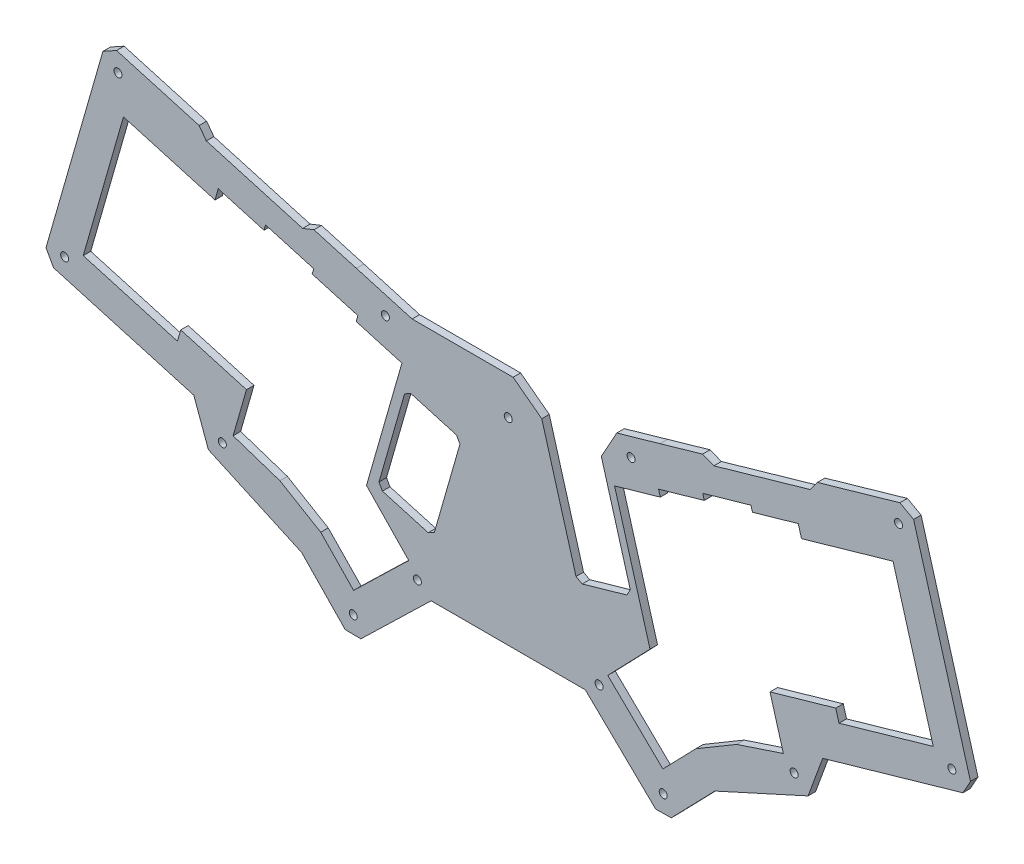
SolidWorks part; units mm, degrees
ref_plane "Plan de face" through (0, 0, 0) normal (0, 0, 1) x (1, 0, 0)
ref_plane "Plan de dessus" through (0, 0, 0) normal (0, 1, 0) x (1, 0, 0)
ref_plane "Plan de droite" through (0, 0, 0) normal (1, 0, 0) x (0, 0, -1)
sketch "Esquisse1" plane through (0, 0, 0) normal (0, 0, 1) x (1, 0, 0)
  line L0 (-121.6461, -32.0475) -> (-108.1875, -28.1884) construction
  line L1 (-108.1875, -28.1884) -> (-104.3283, -41.647) construction
  line L2 (-104.3283, -41.647) -> (-117.7869, -45.5062) construction
  line L3 (-117.7869, -45.5062) -> (-121.6461, -32.0475) construction
  line L4 (-100.1763, -37.9855) -> (-104.0355, -24.5269) construction
  line L5 (-104.0355, -24.5269) -> (-90.5769, -20.6677) construction
  line L6 (-90.5769, -20.6677) -> (-86.7177, -34.1263) construction
  line L7 (-86.7177, -34.1263) -> (-100.1763, -37.9855) construction
  line L8 (-82.5657, -30.4649) -> (-86.4249, -17.0063) construction
  line L9 (-86.4249, -17.0063) -> (-72.9663, -13.1471) construction
  line L10 (-72.9663, -13.1471) -> (-69.1071, -26.6057) construction
  line L11 (-69.1071, -26.6057) -> (-82.5657, -30.4649) construction
  line L12 (-63.6458, -27.5106) -> (-67.505, -14.0519) construction
  line L13 (-67.505, -14.0519) -> (-54.0463, -10.1927) construction
  line L14 (-54.0463, -10.1927) -> (-50.1872, -23.6514) construction
  line L15 (-50.1872, -23.6514) -> (-63.6458, -27.5106) construction
  line L16 (-44.0711, -26.8394) -> (-47.9303, -13.3808) construction
  line L17 (-47.9303, -13.3808) -> (-34.4717, -9.5216) construction
  line L18 (-34.4717, -9.5216) -> (-30.6125, -22.9802) construction
  line L19 (-30.6125, -22.9802) -> (-44.0711, -26.8394) construction
  line L20 (-25.8054, -21.6018) -> (-29.6646, -8.1432) construction
  line L21 (-29.6646, -8.1432) -> (-16.206, -4.284) construction
  line L22 (-16.206, -4.284) -> (-12.3468, -17.7426) construction
  line L23 (-12.3468, -17.7426) -> (-25.8054, -21.6018) construction
  line L24 (-116.4086, -50.3128) -> (-102.95, -46.4536) construction
  line L25 (-102.95, -46.4536) -> (-99.0908, -59.9122) construction
  line L26 (-99.0908, -59.9122) -> (-112.5494, -63.7714) construction
  line L27 (-112.5494, -63.7714) -> (-116.4086, -50.3128) construction
  line L28 (-98.798, -42.7922) -> (-85.3394, -38.933) construction
  line L29 (-85.3394, -38.933) -> (-81.4802, -52.3916) construction
  line L30 (-81.4802, -52.3916) -> (-94.9388, -56.2508) construction
  line L31 (-94.9388, -56.2508) -> (-98.798, -42.7922) construction
  line L32 (-81.1874, -35.2715) -> (-67.7288, -31.4123) construction
  line L33 (-67.7288, -31.4123) -> (-63.8696, -44.8709) construction
  line L34 (-63.8696, -44.8709) -> (-77.3282, -48.7301) construction
  line L35 (-77.3282, -48.7301) -> (-81.1874, -35.2715) construction
  line L36 (-62.2675, -32.3172) -> (-48.8089, -28.458) construction
  line L37 (-48.8089, -28.458) -> (-44.9497, -41.9166) construction
  line L38 (-44.9497, -41.9166) -> (-58.4083, -45.7758) construction
  line L39 (-58.4083, -45.7758) -> (-62.2675, -32.3172) construction
  line L40 (-42.6928, -31.646) -> (-29.2342, -27.7869) construction
  line L41 (-29.2342, -27.7869) -> (-25.375, -41.2455) construction
  line L42 (-25.375, -41.2455) -> (-38.8336, -45.1047) construction
  line L43 (-38.8336, -45.1047) -> (-42.6928, -31.646) construction
  line L44 (-24.4271, -26.4084) -> (-10.9685, -22.5492) construction
  line L45 (-10.9685, -22.5492) -> (-7.1093, -36.0078) construction
  line L46 (-7.1093, -36.0078) -> (-20.5679, -39.867) construction
  line L47 (-20.5679, -39.867) -> (-24.4271, -26.4084) construction
  line L48 (-19.1896, -44.6737) -> (-5.731, -40.8145) construction
  line L49 (-5.731, -40.8145) -> (-1.8718, -54.2731) construction
  line L50 (-1.8718, -54.2731) -> (-15.3304, -58.1323) construction
  line L51 (-15.3304, -58.1323) -> (-19.1896, -44.6737) construction
  line L52 (-37.4554, -49.9113) -> (-23.9967, -46.0521) construction
  line L53 (-23.9967, -46.0521) -> (-20.1376, -59.5107) construction
  line L54 (-20.1376, -59.5107) -> (-33.5962, -63.3699) construction
  line L55 (-33.5962, -63.3699) -> (-37.4554, -49.9113) construction
  line L56 (-57.03, -50.5825) -> (-43.5714, -46.7233) construction
  line L57 (-43.5714, -46.7233) -> (-39.7122, -60.1819) construction
  line L58 (-39.7122, -60.1819) -> (-53.1708, -64.0411) construction
  line L59 (-53.1708, -64.0411) -> (-57.03, -50.5825) construction
  line L60 (-75.9499, -53.5368) -> (-62.4913, -49.6776) construction
  line L61 (-62.4913, -49.6776) -> (-58.6321, -63.1362) construction
  line L62 (-58.6321, -63.1362) -> (-72.0908, -66.9954) construction
  line L63 (-72.0908, -66.9954) -> (-75.9499, -53.5368) construction
  line L64 (-93.5605, -61.0574) -> (-80.1019, -57.1982) construction
  line L65 (-80.1019, -57.1982) -> (-76.2427, -70.6569) construction
  line L66 (-76.2427, -70.6569) -> (-89.7013, -74.516) construction
  line L67 (-89.7013, -74.516) -> (-93.5605, -61.0574) construction
  line L68 (-111.1711, -68.5781) -> (-97.7125, -64.7189) construction
  line L69 (-97.7125, -64.7189) -> (-93.8533, -78.1775) construction
  line L70 (-93.8533, -78.1775) -> (-107.3119, -82.0367) construction
  line L71 (-107.3119, -82.0367) -> (-111.1711, -68.5781) construction
  line L72 (-79.0181, -77.3048) -> (-65.5595, -73.4456) construction
  line L73 (-65.5595, -73.4456) -> (-61.7003, -86.9042) construction
  line L74 (-61.7003, -86.9042) -> (-75.1589, -90.7634) construction
  line L75 (-75.1589, -90.7634) -> (-79.0181, -77.3048) construction
  line L76 (-99.4001, -88.1351) -> (-87.3916, -80.9362) construction
  line L77 (-87.3916, -80.9362) -> (-80.1927, -92.9448) construction
  line L78 (-80.1927, -92.9448) -> (-92.2012, -100.1436) construction
  line L79 (-92.2012, -100.1436) -> (-99.4001, -88.1351) construction
  line L80 (-120.0498, -100.4367) -> (-110.317, -90.3719) construction
  line L81 (-110.317, -90.3719) -> (-100.2522, -100.1047) construction
  line L82 (-100.2522, -100.1047) -> (-109.985, -110.1695) construction
  line L83 (-109.985, -110.1695) -> (-120.0498, -100.4367) construction
  line L86 (0.634, -55.7756) -> (-52.9527, -71.1413) construction
  line L89 (-59.2205, -88.2424) -> (-52.9527, -71.1413) construction
  line L96 (-93.4066, -103.0586) -> (-59.4637, -88.3612) construction
  line L97 (-105.418, -115.2057) -> (-93.9754, -103.3509) construction
  line L98 (-126.5332, -96.9919) -> (-107.5003, -115.385) construction
  line L99 (-167.7972, -50.1766) -> (-183.2082, -64.014) construction
  line L100 (-106.3822, -25.4572) -> (-123.6848, -30.4187) construction
  line L101 (-72.1178, -10.6906) -> (-88.4663, -15.3784) construction
  line L102 (-53.2337, -7.6163) -> (-70.5393, -12.5786) construction
  line L103 (-33.6604, -6.9452) -> (-50.9661, -11.9075) construction
  line L104 (-15.3965, -1.7081) -> (-31.745, -6.396) construction
  line L105 (0.5403, -55.2132) -> (-14.6896, -2.0999) construction
  line L106 (-16.199, -60.6113) -> (0.1495, -55.9235) construction
  line L107 (-52.7198, -71.0835) -> (-18.1144, -61.1606) construction
  line L108 (-59.1184, -88.0534) -> (-52.9674, -71.2752) construction
  line L109 (-183.2082, -64.014) -> (-173.1824, -64.9357) construction
  line L113 (-102.2678, -134.438) -> (-84.7238, -116.3191) construction
  line L114 (-84.7238, -116.3191) -> (-47.2969, -99.2981) construction
  line L115 (-47.2969, -99.2981) -> (-41.4917, -83.4594) construction
  line L116 (14.3812, -67.4381) -> (-41.4917, -83.4594) construction
  line L117 (17.8093, -61.2536) -> (-5.1371, 18.7701) construction
  line L122 (-11.3217, 22.1985) -> (-107.4545, -5.3614) construction
  line L129 (-167.7953, -27.6055) -> (-167.7953, -64.7189) construction
  line L130 (-242.0685, -103.8419) -> (-276.37, -88.2424) construction
  line L131 (-229.5108, -116.8112) -> (-242.0685, -103.8419) construction
  line L138 (-208.9328, -96.8551) -> (-229.5108, -116.8112) construction
  line L139 (-225.5107, -79.6567) -> (-208.9328, -96.8551) construction
  line L140 (-109.3352, -134.5492) -> (-102.2678, -134.438) construction
  line L142 (-5.1371, 18.7701) -> (-11.3217, 22.1985) construction
  line L143 (-211.4691, -30.6868) -> (-225.5107, -79.6567) construction
  line L147 (-114.18, -7.2899) -> (-107.4545, -5.3614) construction
  line L148 (-114.18, -7.2899) -> (-123.7936, -10.0465) construction
  line L154 (-118.7579, -16.9241) -> (-12.0005, 13.6817) construction
  line L155 (-131.531, -101.8802) -> (-105.9239, -126.7133) construction
  line L156 (-105.9239, -126.7133) -> (-89.4162, -109.6646) construction
  line L157 (-128.0696, -96.8789) -> (-106.0575, -118.2258)
  line L158 (-106.0575, -118.2258) -> (-92.9354, -104.6737)
  line L159 (-92.9354, -104.6737) -> (-58.4256, -88.9794) construction
  line L161 (1.8709, -56.4612) -> (-35.7408, -67.2462)
  line L162 (1.8709, -56.4612) -> (-14.1861, -0.4639)
  line L163 (-14.1861, -0.4639) -> (-50.7166, -10.9388)
  line L164 (-50.7166, -10.9388) -> (-52.026, -6.3725)
  line L165 (-52.026, -6.3725) -> (-70.2913, -11.61)
  line L166 (-70.2913, -11.61) -> (-70.911, -9.4488)
  line L167 (-70.911, -9.4488) -> (-90.1377, -14.9608)
  line L168 (-90.1377, -14.9608) -> (-89.5177, -17.1231)
  line L169 (-89.5177, -17.1231) -> (-107.783, -22.3606)
  line L170 (-107.783, -22.3606) -> (-107.0938, -24.7639)
  line L171 (-107.0938, -24.7639) -> (-125.3583, -30.0011)
  line L172 (-125.3583, -30.0011) -> (-111.2001, -79.378)
  line L173 (-111.2001, -79.378) -> (-127.3777, -96.1611)
  line L174 (-89.4162, -109.6646) -> (-53.6562, -93.4017) construction
  line L175 (-53.6562, -93.4017) -> (-47.6042, -76.8897) construction
  line L176 (9.2923, -60.5749) -> (-47.6042, -76.8897) construction
  line L177 (9.2923, -60.5749) -> (-12.0005, 13.6817) construction
  line L178 (-229.7336, -25.4495) -> (-211.4691, -30.6868) construction
  line L179 (-229.0444, -23.0462) -> (-229.7336, -25.4495) construction
  line L180 (-173.1824, -64.9357) -> (-167.7972, -60.1004) construction
  line L181 (-247.3097, -17.8087) -> (-229.0444, -23.0462) construction
  line L185 (17.8093, -61.2536) -> (14.3812, -67.4381) construction
  line L186 (-183.2987, -65.7677) -> (-173.2729, -66.6895) construction
  line L187 (-173.2729, -66.6895) -> (-167.8052, -74.7882) construction
  line L190 (-246.6897, -15.6465) -> (-247.3097, -17.8087) construction
  line L191 (-263.9939, -10.6857) -> (-246.6897, -15.6465) construction
  line L192 (-264.6136, -12.8469) -> (-263.9939, -10.6857) construction
  line L193 (-282.8789, -7.6094) -> (-264.6136, -12.8469) construction
  line L194 (-284.1883, -12.1757) -> (-282.8789, -7.6094) construction
  line L195 (-320.7188, -1.7008) -> (-284.1883, -12.1757) construction
  line L196 (-336.2245, -55.7756) -> (-320.7188, -1.7008) construction
  line L197 (-183.2987, -65.7677) -> (-167.8052, -88.0782) construction
  line L198 (-181.8414, -71.5322) -> (-174.8684, -81.0171) construction
  line L199 (-174.8684, -81.0171) -> (-178.3549, -83.9622) construction
  line L200 (-344.8828, -60.5749) -> (-323.5901, 13.6817) construction
  line L201 (-344.8828, -60.5749) -> (-287.9863, -76.8897) construction
  line L202 (-281.9343, -93.4017) -> (-287.9863, -76.8897) construction
  line L203 (-246.1743, -109.6646) -> (-281.9343, -93.4017) construction
  line L204 (-224.3904, -79.378) -> (-208.2128, -96.1611)
  line L205 (-210.2322, -30.0011) -> (-224.3904, -79.378)
  line L206 (-228.4967, -24.7639) -> (-210.2322, -30.0011)
  line L207 (-227.8075, -22.3606) -> (-228.4967, -24.7639)
  line L208 (-246.0728, -17.1231) -> (-227.8075, -22.3606)
  line L209 (-245.4528, -14.9608) -> (-246.0728, -17.1231)
  line L210 (-264.6796, -9.4488) -> (-245.4528, -14.9608)
  line L211 (-265.2993, -11.61) -> (-264.6796, -9.4488)
  line L212 (-283.5645, -6.3725) -> (-265.2993, -11.61)
  line L213 (-284.8739, -10.9388) -> (-283.5645, -6.3725)
  line L217 (0.634, -55.7756) -> (-14.8717, -1.7008) construction
  line L220 (-14.8717, -1.7008) -> (-51.4022, -12.1757) construction
  line L221 (-51.4022, -12.1757) -> (-52.7116, -7.6094) construction
  line L222 (-52.7116, -7.6094) -> (-70.9769, -12.8469) construction
  line L223 (-70.9769, -12.8469) -> (-71.5966, -10.6857) construction
  line L224 (-71.5966, -10.6857) -> (-88.9008, -15.6465) construction
  line L225 (-88.9008, -15.6465) -> (-88.2808, -17.8087) construction
  line L226 (-88.2808, -17.8087) -> (-106.5461, -23.0462) construction
  line L227 (-106.5461, -23.0462) -> (-105.8569, -25.4495) construction
  line L228 (-105.8569, -25.4495) -> (-124.1214, -30.6868) construction
  line L231 (-124.1214, -30.6868) -> (-110.0799, -79.6567) construction
  line L232 (-110.0799, -79.6567) -> (-126.6577, -96.8551) construction
  line L233 (-126.6577, -96.8551) -> (-106.0797, -116.8112) construction
  line L234 (-106.0797, -116.8112) -> (-93.522, -103.8419) construction
  line L235 (-93.522, -103.8419) -> (-59.2205, -88.2424) construction
  line L236 (-321.4044, -0.4639) -> (-284.8739, -10.9388)
  line L237 (-337.4614, -56.4612) -> (-321.4044, -0.4639)
  line L238 (-337.4614, -56.4612) -> (-299.8497, -67.2462)
  line L241 (-229.5331, -118.2258) -> (-242.6551, -104.6737)
  line L242 (-208.2366, -97.573) -> (-229.5331, -118.2258)
  line L243 (-229.6666, -126.7133) -> (-246.1743, -109.6646) construction
  line L244 (-204.0596, -101.8802) -> (-229.6666, -126.7133) construction
  line L245 (-331.2803, 15.8863) -> (-193.4471, -23.6284) construction
  line L246 (-178.3549, -83.9622) -> (-185.8788, -75.0552) construction
  line L247 (-185.8788, -75.0552) -> (-181.8414, -71.5322) construction
  line L248 (-176.7625, -46.6332) -> (-185.5498, -54.5291) construction
  line L249 (-185.5498, -54.5291) -> (-181.1562, -59.4188) construction
  line L250 (-181.1562, -59.4188) -> (-172.3689, -51.5229) construction
  line L251 (-276.4721, -88.0534) -> (-282.6232, -71.2752) construction
  line L252 (-282.8707, -71.0835) -> (-317.4761, -61.1606) construction
  line L253 (-319.3915, -60.6113) -> (-335.74, -55.9235) construction
  line L254 (-336.1309, -55.2132) -> (-320.9009, -2.0999) construction
  line L255 (-320.194, -1.7081) -> (-303.8455, -6.396) construction
  line L256 (-301.9301, -6.9452) -> (-284.6245, -11.9075) construction
  line L257 (-282.3568, -7.6163) -> (-265.0512, -12.5786) construction
  line L258 (-263.4727, -10.6906) -> (-247.1242, -15.3784) construction
  line L259 (-229.2083, -25.4572) -> (-211.9057, -30.4187) construction
  line L260 (-172.3689, -51.5229) -> (-176.7625, -46.6332) construction
  line L261 (-209.0573, -96.9919) -> (-228.0902, -115.385) construction
  line L262 (-230.1725, -115.2057) -> (-241.6151, -103.3509) construction
  line L263 (-242.1839, -103.0586) -> (-276.1268, -88.3612) construction
  line L264 (-276.37, -88.2424) -> (-282.6379, -71.1413) construction
  line L265 (-336.2245, -55.7756) -> (-282.6379, -71.1413) construction
  line L268 (-353.3998, -61.2536) -> (-349.9717, -67.4381) construction
  line L274 (-221.4105, -7.2899) -> (-206.0252, -11.7015) construction
  line L275 (-221.4105, -7.2899) -> (-228.136, -5.3614) construction
  line L276 (-330.4534, 18.7701) -> (-324.2688, 22.1985) construction
  line L277 (-226.2553, -134.5492) -> (-233.3227, -134.438) construction
  line L281 (-324.2688, 22.1985) -> (-228.136, -5.3614) construction
  line L282 (-353.3998, -61.2536) -> (-330.4534, 18.7701) construction
  line L283 (-349.9717, -67.4381) -> (-294.0988, -83.4594) construction
  line L284 (-288.2936, -99.2981) -> (-294.0988, -83.4594) construction
  line L285 (-250.8667, -116.3191) -> (-288.2936, -99.2981) construction
  line L286 (-233.3227, -134.438) -> (-250.8667, -116.3191) construction
  line L288 (-225.6055, -110.1695) -> (-215.5407, -100.4367) construction
  line L289 (-235.3383, -100.1047) -> (-225.6055, -110.1695) construction
  line L290 (-225.2735, -90.3719) -> (-235.3383, -100.1047) construction
  line L291 (-215.5407, -100.4367) -> (-225.2735, -90.3719) construction
  line L292 (-243.3893, -100.1436) -> (-236.1904, -88.1351) construction
  line L293 (-255.3978, -92.9448) -> (-243.3893, -100.1436) construction
  line L294 (-248.1989, -80.9362) -> (-255.3978, -92.9448) construction
  line L295 (-236.1904, -88.1351) -> (-248.1989, -80.9362) construction
  line L296 (-260.4316, -90.7634) -> (-256.5724, -77.3048) construction
  line L297 (-273.8902, -86.9042) -> (-260.4316, -90.7634) construction
  line L298 (-270.031, -73.4456) -> (-273.8902, -86.9042) construction
  line L299 (-256.5724, -77.3048) -> (-270.031, -73.4456) construction
  line L300 (-228.2786, -82.0367) -> (-224.4194, -68.5781) construction
  line L301 (-241.7372, -78.1775) -> (-228.2786, -82.0367) construction
  line L302 (-237.878, -64.7189) -> (-241.7372, -78.1775) construction
  line L303 (-224.4194, -68.5781) -> (-237.878, -64.7189) construction
  line L304 (-245.8892, -74.516) -> (-242.03, -61.0574) construction
  line L305 (-259.3478, -70.6569) -> (-245.8892, -74.516) construction
  line L306 (-255.4886, -57.1982) -> (-259.3478, -70.6569) construction
  line L307 (-242.03, -61.0574) -> (-255.4886, -57.1982) construction
  line L308 (-263.4998, -66.9954) -> (-259.6406, -53.5368) construction
  line L309 (-276.9584, -63.1362) -> (-263.4998, -66.9954) construction
  line L310 (-273.0992, -49.6776) -> (-276.9584, -63.1362) construction
  line L311 (-259.6406, -53.5368) -> (-273.0992, -49.6776) construction
  line L312 (-282.4197, -64.0411) -> (-278.5605, -50.5825) construction
  line L313 (-295.8783, -60.1819) -> (-282.4197, -64.0411) construction
  line L314 (-292.0191, -46.7233) -> (-295.8783, -60.1819) construction
  line L315 (-278.5605, -50.5825) -> (-292.0191, -46.7233) construction
  line L316 (-301.9944, -63.3699) -> (-298.1352, -49.9113) construction
  line L317 (-315.453, -59.5107) -> (-301.9944, -63.3699) construction
  line L318 (-311.5938, -46.0521) -> (-315.453, -59.5107) construction
  line L319 (-298.1352, -49.9113) -> (-311.5938, -46.0521) construction
  line L320 (-320.2601, -58.1323) -> (-316.4009, -44.6737) construction
  line L321 (-333.7187, -54.2731) -> (-320.2601, -58.1323) construction
  line L322 (-329.8595, -40.8145) -> (-333.7187, -54.2731) construction
  line L323 (-316.4009, -44.6737) -> (-329.8595, -40.8145) construction
  line L324 (-315.0226, -39.867) -> (-311.1634, -26.4084) construction
  line L325 (-328.4812, -36.0078) -> (-315.0226, -39.867) construction
  line L326 (-324.622, -22.5492) -> (-328.4812, -36.0078) construction
  line L327 (-311.1634, -26.4084) -> (-324.622, -22.5492) construction
  line L328 (-296.7569, -45.1047) -> (-292.8977, -31.646) construction
  line L329 (-310.2155, -41.2455) -> (-296.7569, -45.1047) construction
  line L330 (-306.3563, -27.7869) -> (-310.2155, -41.2455) construction
  line L331 (-292.8977, -31.646) -> (-306.3563, -27.7869) construction
  line L332 (-277.1822, -45.7758) -> (-273.323, -32.3172) construction
  line L333 (-290.6408, -41.9166) -> (-277.1822, -45.7758) construction
  line L334 (-286.7817, -28.458) -> (-290.6408, -41.9166) construction
  line L335 (-273.323, -32.3172) -> (-286.7817, -28.458) construction
  line L336 (-258.2623, -48.7301) -> (-254.4031, -35.2715) construction
  line L337 (-271.7209, -44.8709) -> (-258.2623, -48.7301) construction
  line L338 (-267.8617, -31.4123) -> (-271.7209, -44.8709) construction
  line L339 (-254.4031, -35.2715) -> (-267.8617, -31.4123) construction
  line L340 (-240.6517, -56.2508) -> (-236.7925, -42.7922) construction
  line L341 (-254.1103, -52.3916) -> (-240.6517, -56.2508) construction
  line L342 (-250.2511, -38.933) -> (-254.1103, -52.3916) construction
  line L343 (-236.7925, -42.7922) -> (-250.2511, -38.933) construction
  line L344 (-223.0411, -63.7714) -> (-219.1819, -50.3128) construction
  line L345 (-236.4997, -59.9122) -> (-223.0411, -63.7714) construction
  line L346 (-232.6405, -46.4536) -> (-236.4997, -59.9122) construction
  line L347 (-219.1819, -50.3128) -> (-232.6405, -46.4536) construction
  line L348 (-323.2438, -17.7426) -> (-309.7851, -21.6018) construction
  line L349 (-319.3846, -4.284) -> (-323.2438, -17.7426) construction
  line L350 (-305.926, -8.1432) -> (-319.3846, -4.284) construction
  line L351 (-309.7851, -21.6018) -> (-305.926, -8.1432) construction
  line L352 (-304.978, -22.9802) -> (-291.5194, -26.8394) construction
  line L353 (-301.1188, -9.5216) -> (-304.978, -22.9802) construction
  line L354 (-287.6602, -13.3808) -> (-301.1188, -9.5216) construction
  line L355 (-291.5194, -26.8394) -> (-287.6602, -13.3808) construction
  line L356 (-285.4034, -23.6514) -> (-271.9448, -27.5106) construction
  line L357 (-281.5442, -10.1927) -> (-285.4034, -23.6514) construction
  line L358 (-268.0856, -14.0519) -> (-281.5442, -10.1927) construction
  line L359 (-271.9448, -27.5106) -> (-268.0856, -14.0519) construction
  line L360 (-266.4834, -26.6057) -> (-253.0248, -30.4649) construction
  line L361 (-262.6242, -13.1471) -> (-266.4834, -26.6057) construction
  line L362 (-249.1656, -17.0063) -> (-262.6242, -13.1471) construction
  line L363 (-253.0248, -30.4649) -> (-249.1656, -17.0063) construction
  line L364 (-248.8728, -34.1263) -> (-235.4142, -37.9855) construction
  line L365 (-245.0136, -20.6677) -> (-248.8728, -34.1263) construction
  line L366 (-231.555, -24.5269) -> (-245.0136, -20.6677) construction
  line L367 (-235.4142, -37.9855) -> (-231.555, -24.5269) construction
  line L368 (-217.8036, -45.5062) -> (-213.9444, -32.0475) construction
  line L369 (-231.2622, -41.647) -> (-217.8036, -45.5062) construction
  line L370 (-227.4031, -28.1884) -> (-231.2622, -41.647) construction
  line L371 (-213.9444, -32.0475) -> (-227.4031, -28.1884) construction
  line L372 (-226.2553, -134.5492) -> (-194.0347, -103.3509) construction
  line L373 (-109.3352, -134.5492) -> (-141.5559, -103.3509) construction
  line L374 (-141.5559, -103.3509) -> (-194.0347, -103.3509) construction
  line L375 (-167.7972, -50.1766) -> (-152.3861, -64.014) construction
  line L376 (-162.4119, -64.9357) -> (-167.7972, -60.1004) construction
  line L377 (-162.3376, -66.6895) -> (-167.8052, -74.7882) construction
  line L378 (-152.3118, -65.7677) -> (-167.8052, -88.0782) construction
  line L379 (-163.2254, -51.5229) -> (-158.8318, -46.6332) construction
  line L380 (-154.4381, -59.4188) -> (-163.2254, -51.5229) construction
  line L381 (-150.0445, -54.5291) -> (-154.4381, -59.4188) construction
  line L382 (-158.8318, -46.6332) -> (-150.0445, -54.5291) construction
  line L383 (-149.7316, -75.0552) -> (-153.7691, -71.5322) construction
  line L384 (-157.2555, -83.9622) -> (-149.7316, -75.0552) construction
  line L385 (-160.742, -81.0171) -> (-157.2555, -83.9622) construction
  line L386 (-153.7691, -71.5322) -> (-160.742, -81.0171) construction
  line L387 (-152.3118, -65.7677) -> (-162.3376, -66.6895) construction
  line L388 (-152.3861, -64.014) -> (-162.4119, -64.9357) construction
  line L389 (-206.0252, -11.7015) -> (-129.5654, -11.7015) construction
  line L390 (-119.0708, -62.7964) -> (-130.6498, -22.4155)
  line L391 (-123.5545, -47.16) -> (-127.4136, -33.7014) construction
  line L392 (-120.442, -65.2702) -> (-138.2688, -70.3819)
  line L393 (-140.7426, -69.0107) -> (-154.4194, -21.3141)
  line L394 (-167.1758, -11.7015) -> (-206.0252, -11.7015) construction
  line L395 (-154.4194, -21.3141) -> (-167.1758, -11.7015) construction
  line L396 (-123.7936, -10.0465) -> (-130.6498, -22.4155) construction
  line L397 (-138.2688, -70.3819) -> (-140.7426, -69.0107)
  line L398 (-119.0708, -62.7964) -> (-120.442, -65.2702)
  line L399 (-129.5654, -11.7015) -> (-123.7936, -10.0465) construction
  line L400 (-165.8487, -12.7015) -> (-206.1657, -12.7015)
  line L401 (-221.6861, -8.2511) -> (-206.1657, -12.7015)
  line L402 (-221.6861, -8.2511) -> (-228.4116, -6.3226)
  line L403 (-324.1462, 21.1231) -> (-291.1905, 11.6751)
  line L404 (-329.6063, 18.0963) -> (-324.1462, 21.1231)
  line L405 (-352.3244, -61.1311) -> (-329.6063, 18.0963)
  line L406 (-352.3244, -61.1311) -> (-349.2979, -66.591)
  line L407 (-349.2979, -66.591) -> (-293.3347, -82.6382)
  line L408 (-287.4987, -98.561) -> (-293.3347, -82.6382)
  line L409 (-250.2802, -115.4872) -> (-287.4987, -98.561)
  line L410 (-232.8926, -133.4446) -> (-250.2802, -115.4872)
  line L411 (-226.6535, -133.5428) -> (-232.8926, -133.4446)
  line L412 (-226.6535, -133.5428) -> (-198.5705, -106.3509)
  line L413 (-141.1511, -102.3509) -> (-194.4395, -102.3509) construction
  line L414 (-108.937, -133.5428) -> (-137.02, -106.3509)
  line L415 (-108.937, -133.5428) -> (-102.6979, -133.4446)
  line L416 (-102.6979, -133.4446) -> (-85.3104, -115.4872)
  line L417 (-85.3104, -115.4872) -> (-48.0918, -98.561)
  line L418 (-48.0918, -98.561) -> (-42.2558, -82.6382)
  line L419 (13.7074, -66.591) -> (-42.2558, -82.6382)
  line L420 (16.7339, -61.1311) -> (13.7074, -66.591)
  line L421 (16.7339, -61.1311) -> (-5.9842, 18.0963)
  line L422 (-5.9842, 18.0963) -> (-11.4443, 21.1231)
  line L423 (-11.4443, 21.1231) -> (-44.4001, 11.6751)
  line L424 (-113.9044, -8.2511) -> (-107.1789, -6.3226)
  line L425 (-113.9044, -8.2511) -> (-124.4792, -11.2834)
  line L426 (-167.1758, -12.7015) -> (-206.1657, -12.7015) construction
  line L427 (-113.9044, -8.2511) -> (-123.5179, -11.0078) construction
  line L428 (-165.8487, -12.7015) -> (-154.4194, -21.3141)
  line L429 (-130.6498, -22.4155) -> (-124.4792, -11.2834)
  line L430 (-208.2366, -97.573) -> (-207.4919, -96.8551)
  line L431 (-207.4919, -96.8551) -> (-208.2128, -96.1611)
  line L432 (-127.3777, -96.1611) -> (-128.0696, -96.8789)
  line L433 (-132.8889, -110.3509) -> (-202.7016, -110.3509) construction
  line L434 (-141.1511, -110.3509) -> (-194.4395, -110.3509) construction
  line L435 (-87.3916, -80.9362) -> (-92.2012, -100.1436) construction
  line L436 (-226.6535, -133.5428) -> (-194.4395, -102.3509) construction
  line L437 (-108.937, -133.5428) -> (-141.1511, -102.3509) construction
  line L438 (-65.5595, -73.4456) -> (-75.1589, -90.7634) construction
  line L439 (-59.5038, -49.2112) -> (-42.2001, -44.2495) construction
  line L440 (-92.8883, -102.8873) -> (-102.1438, -87.448) construction
  line L441 (-102.1438, -87.448) -> (-86.7045, -78.1925) construction
  line L442 (-86.7045, -78.1925) -> (-77.449, -93.6318) construction
  line L443 (-77.449, -93.6318) -> (-92.8883, -102.8873) construction
  line L444 (-76.5302, -93.2372) -> (-81.4919, -75.9335) construction
  line L445 (-81.4919, -75.9335) -> (-64.1883, -70.9718) construction
  line L446 (-64.1883, -70.9718) -> (-59.2265, -88.2755) construction
  line L447 (-59.2265, -88.2755) -> (-76.5302, -93.2372) construction
  line L448 (-42.2001, -44.2495) -> (-37.2384, -61.5531) construction
  line L449 (-37.2384, -61.5531) -> (-54.5421, -66.5149) construction
  line L450 (-54.5421, -66.5149) -> (-59.5038, -49.2112) construction
  line L451 (-76.6212, -95.0127) -> (-92.0605, -104.2682) construction
  line L452 (-92.9354, -104.6737) -> (-76.6212, -95.0127)
  line L453 (-76.6212, -95.0127) -> (-57.9612, -88.8254)
  line L454 (-39.9292, -48.5401) -> (-22.6255, -43.5783) construction
  line L455 (-22.6255, -43.5783) -> (-17.6638, -60.882) construction
  line L456 (-17.6638, -60.882) -> (-34.9674, -65.8437) construction
  line L457 (-34.9674, -65.8437) -> (-39.9292, -48.5401) construction
  line L458 (-63.102, -70.6603) -> (-58.1403, -87.964) construction
  line L459 (-36.9269, -62.6394) -> (-54.2306, -67.6011) construction
  line L460 (-36.0536, -66.1552) -> (-41.0154, -48.8515) construction
  line L461 (-57.9612, -88.8254) -> (-63.3014, -70.2021)
  line L462 (-37.0515, -62.6751) -> (-63.3014, -70.2021)
  line L463 (-37.0515, -62.6751) -> (-35.7408, -67.2462)
  line L464 (-298.539, -62.6751) -> (-299.8497, -67.2462)
  line L465 (-298.539, -62.6751) -> (-272.2891, -70.2021)
  line L466 (-277.6293, -88.8254) -> (-272.2891, -70.2021)
  line L467 (-258.9693, -95.0127) -> (-277.6293, -88.8254)
  line L468 (-242.6551, -104.6737) -> (-258.9693, -95.0127)
  line L469 (-98.0641, -3.7095) -> (-90.2165, -1.4597)
  line L470 (-94.657, -1.6925) -> (-56.2059, 9.3309) construction
  line L471 (-94.657, -1.6925) -> (-56.2059, 9.3309) construction
  line L474 (-98.0641, -3.7095) -> (-107.1789, -6.3226)
  line L476 (-11.4443, 21.1231) -> (-107.1789, -6.3226) construction
  line L481 (-237.5264, -3.7095) -> (-228.4116, -6.3226)
  line L482 (-66.4927, 2.2629) -> (-65.3792, -1.6212) construction
  line L483 (-324.1462, 21.1231) -> (-228.4116, -6.3226) construction
  line L484 (-85.7183, -3.2488) -> (-47.2672, 7.7746)
  line L485 (-90.2165, -1.4597) -> (-85.7183, -3.2488)
  line L486 (-44.4001, 11.6751) -> (-47.2672, 7.7746)
  line L487 (-291.1905, 11.6751) -> (-288.3233, 7.7746)
  line L488 (-249.8723, -3.2488) -> (-288.3233, 7.7746)
  line L489 (-245.374, -1.4597) -> (-249.8723, -3.2488)
  line L490 (-245.374, -1.4597) -> (-237.5264, -3.7095)
  line L491 (-134.9544, -108.3509) -> (-200.6361, -108.3509) construction
  line L492 (-137.02, -106.3509) -> (-198.5705, -106.3509)
  line L493 (-132.8889, -108.3509) -> (-202.7016, -108.3509) construction
  line L494 (-197.2749, -82.0103) -> (-187.0783, -46.443)
  line L495 (-134.9544, -106.3509) -> (-200.6361, -106.3509) construction
  line L504 (-188.4497, -43.9693) -> (-206.714, -38.7332)
  line L505 (-219.3843, -75.6719) -> (-209.1877, -40.1046)
  line L506 (-199.7487, -83.3817) -> (-218.0129, -78.1456)
  line L507 (-206.714, -38.7332) -> (-209.1877, -40.1046)
  line L508 (-187.0783, -46.443) -> (-188.4497, -43.9693)
  line L509 (-199.7487, -83.3817) -> (-197.2749, -82.0103)
  line L510 (-218.0129, -78.1456) -> (-219.3843, -75.6719)
  line L511 (-192.1766, -64.2267) -> (-167.7953, -64.7189) construction
  circle A2 centre (-12.0005, 13.6817) radius 1.6
  circle A3 centre (-12.0005, 13.6817) radius 3 construction
  circle A4 centre (-118.7579, -16.9241) radius 1.6
  circle A5 centre (9.2923, -60.5749) radius 1.6
  circle A6 centre (-53.6562, -93.4017) radius 1.6
  circle A7 centre (-105.9239, -126.7133) radius 1.6
  circle A8 centre (-131.531, -101.8802) radius 1.6
  circle A10 centre (-147.4897, -45.973) radius 1.6 construction
  circle A11 centre (-323.5901, 13.6817) radius 3 construction
  circle A12 centre (-188.1008, -45.973) radius 1.6 construction
  circle A14 centre (-204.0596, -101.8802) radius 1.6
  circle A15 centre (-229.6666, -126.7133) radius 1.6
  circle A16 centre (-281.9343, -93.4017) radius 1.6
  circle A17 centre (-344.8828, -60.5749) radius 1.6
  circle A18 centre (-216.8326, -16.9241) radius 1.6
  circle A19 centre (-323.5901, 13.6817) radius 1.6
  circle A20 centre (-167.7953, -27.6055) radius 1.6
  point P138 (-167.7953, -27.6055)
  point P139 (-6.5153, 23.5764)
  point P150 (-169.1046, -23.0392)
  point P172 (-65.3792, -1.6212)
  point P200 (19.1875, -66.0599)
  point P203 (-141.5228, -71.3355)
  point P204 (-141.5228, 1.5705)
  point P263 (-133.4062, -12.8029)
  point P264 (-118.5195, -64.7189)
  point P283 (-140.1914, -70.9332)
  point P284 (-157.1758, -11.7015)
  point P405 (-354.778, -66.0599)
  point P406 (-329.0752, 23.5764)
  point P470 (-75.4315, 3.8192)
  point P473 (-75.4315, 3.8192)
  point P501 (0, 0)
  point P503 (0, 0)
  point P504 (0, 0)
  point P505 (0, 0)
  point P506 (0, 0)
  dimension "D3" = 3.2
  dimension "D4" = 6
  dimension "D6" = 3.2
  dimension "D7" = 3.2
  dimension "D8" = 3.2
  dimension "D9" = 3.2
  dimension "D10" = 3.2
  dimension "D16" = 3.2
  dimension "D2" = 6
  dimension "D5" = 1
  dimension "D14" = 2
  dimension "D21" = 1.61
  dimension "D22" = 2
  dimension "D23" = 1.1349
  dimension "D24" = 1.13
  dimension "D27" = 40
  dimension "D28" = 2
  dimension "D11" = 8
  dimension "D18" = 2
  dimension "D20" = 2
  dimension "D25" = 1.13
  dimension "D26" = 1.13
  dimension "D29" = 2
extrude "Boss.-Extru.1" add sketch "Esquisse1" along normal blind 3 contours L429 L390 L398 L392 L397 L393 L428 L400 L401 L402 L403 L404 L405 L406 L407 L408 L409 L410 L411 L412 L413 L414 L415 L416 L417 L418 L419 L420 L421 L422 L423 L424 L425 A19 A17 A15 L431 L430 L242 L241 L238 L237 L236 L213 L212 region at (-168.2572, -54.7305, 0)
sketch "Esquisse2" plane through (0, 0, 3) normal (0, 0, 1) x (1, 0, 0)
  line L0 (-167.7953, -110.3509) -> (-167.7953, -102.3509) construction
  line L1 (-132.8889, -110.3509) -> (-202.7016, -110.3509) construction
  line L2 (-168.7953, -110.3509) -> (-168.7953, -102.3509)
  line L3 (-166.7953, -110.3509) -> (-166.7953, -102.3509)
  line L4 (-163.7953, -110.3509) -> (-163.7953, -102.3509) construction
  line L5 (-164.7953, -110.3509) -> (-164.7953, -102.3509)
  line L6 (-162.7953, -110.3509) -> (-162.7953, -102.3509)
  line L7 (-159.7953, -110.3509) -> (-159.7953, -102.3509) construction
  line L8 (-160.7953, -110.3509) -> (-160.7953, -102.3509)
  line L9 (-158.7953, -110.3509) -> (-158.7953, -102.3509)
  line L10 (-155.7953, -110.3509) -> (-155.7953, -102.3509) construction
  line L11 (-156.7953, -110.3509) -> (-156.7953, -102.3509)
  line L12 (-154.7953, -110.3509) -> (-154.7953, -102.3509)
  line L13 (-151.7953, -110.3509) -> (-151.7953, -102.3509) construction
  line L14 (-152.7953, -110.3509) -> (-152.7953, -102.3509)
  line L15 (-150.7953, -110.3509) -> (-150.7953, -102.3509)
  line L16 (-147.7953, -110.3509) -> (-147.7953, -102.3509) construction
  line L17 (-148.7953, -110.3509) -> (-148.7953, -102.3509)
  line L18 (-146.7953, -110.3509) -> (-146.7953, -102.3509)
  line L19 (-171.7953, -110.3509) -> (-171.7953, -102.3509) construction
  line L20 (-172.7953, -110.3509) -> (-172.7953, -102.3509)
  line L21 (-170.7953, -110.3509) -> (-170.7953, -102.3509)
  line L22 (-175.7953, -110.3509) -> (-175.7953, -102.3509) construction
  line L23 (-176.7953, -110.3509) -> (-176.7953, -102.3509)
  line L24 (-174.7953, -110.3509) -> (-174.7953, -102.3509)
  line L25 (-179.7953, -110.3509) -> (-179.7953, -102.3509) construction
  line L26 (-180.7953, -110.3509) -> (-180.7953, -102.3509)
  line L27 (-178.7953, -110.3509) -> (-178.7953, -102.3509)
  line L28 (-183.7953, -110.3509) -> (-183.7953, -102.3509) construction
  line L29 (-184.7953, -110.3509) -> (-184.7953, -102.3509)
  line L30 (-182.7953, -110.3509) -> (-182.7953, -102.3509)
  line L31 (-187.7953, -110.3509) -> (-187.7953, -102.3509) construction
  line L32 (-188.7953, -110.3509) -> (-188.7953, -102.3509)
  line L33 (-186.7953, -110.3509) -> (-186.7953, -102.3509)
  arc A0 (-168.7953, -110.3509) -> (-166.7953, -110.3509) centre (-167.7953, -110.3509) ccw
  arc A1 (-166.7953, -102.3509) -> (-168.7953, -102.3509) centre (-167.7953, -102.3509) ccw
  arc A2 (-164.7953, -110.3509) -> (-162.7953, -110.3509) centre (-163.7953, -110.3509) ccw
  arc A3 (-162.7953, -102.3509) -> (-164.7953, -102.3509) centre (-163.7953, -102.3509) ccw
  arc A4 (-160.7953, -110.3509) -> (-158.7953, -110.3509) centre (-159.7953, -110.3509) ccw
  arc A5 (-158.7953, -102.3509) -> (-160.7953, -102.3509) centre (-159.7953, -102.3509) ccw
  arc A6 (-156.7953, -110.3509) -> (-154.7953, -110.3509) centre (-155.7953, -110.3509) ccw
  arc A7 (-154.7953, -102.3509) -> (-156.7953, -102.3509) centre (-155.7953, -102.3509) ccw
  arc A8 (-152.7953, -110.3509) -> (-150.7953, -110.3509) centre (-151.7953, -110.3509) ccw
  arc A9 (-150.7953, -102.3509) -> (-152.7953, -102.3509) centre (-151.7953, -102.3509) ccw
  arc A10 (-148.7953, -110.3509) -> (-146.7953, -110.3509) centre (-147.7953, -110.3509) ccw
  arc A11 (-146.7953, -102.3509) -> (-148.7953, -102.3509) centre (-147.7953, -102.3509) ccw
  arc A12 (-172.7953, -110.3509) -> (-170.7953, -110.3509) centre (-171.7953, -110.3509) ccw
  arc A13 (-170.7953, -102.3509) -> (-172.7953, -102.3509) centre (-171.7953, -102.3509) ccw
  arc A14 (-176.7953, -110.3509) -> (-174.7953, -110.3509) centre (-175.7953, -110.3509) ccw
  arc A15 (-174.7953, -102.3509) -> (-176.7953, -102.3509) centre (-175.7953, -102.3509) ccw
  arc A16 (-180.7953, -110.3509) -> (-178.7953, -110.3509) centre (-179.7953, -110.3509) ccw
  arc A17 (-178.7953, -102.3509) -> (-180.7953, -102.3509) centre (-179.7953, -102.3509) ccw
  arc A18 (-184.7953, -110.3509) -> (-182.7953, -110.3509) centre (-183.7953, -110.3509) ccw
  arc A19 (-182.7953, -102.3509) -> (-184.7953, -102.3509) centre (-183.7953, -102.3509) ccw
  arc A20 (-188.7953, -110.3509) -> (-186.7953, -110.3509) centre (-187.7953, -110.3509) ccw
  arc A21 (-186.7953, -102.3509) -> (-188.7953, -102.3509) centre (-187.7953, -102.3509) ccw
  point P4 (-167.7953, -106.3509)
  point P13 (-163.7953, -106.3509)
  point P20 (-159.7953, -106.3509)
  point P27 (-155.7953, -106.3509)
  point P34 (-151.7953, -106.3509)
  point P41 (-147.7953, -106.3509)
  point P47 (-171.7953, -106.3509)
  point P54 (-175.7953, -106.3509)
  point P61 (-179.7953, -106.3509)
  point P68 (-183.7953, -106.3509)
  point P75 (-187.7953, -106.3509)
  dimension "D1" = 6
  dimension "D2" = 6
